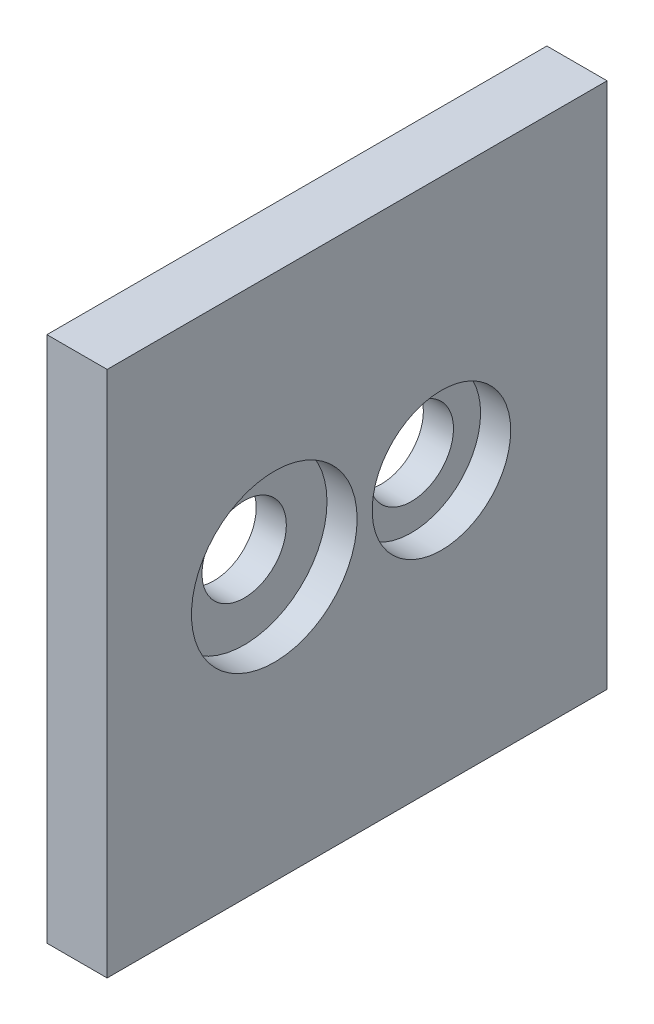
SolidWorks part; units mm, degrees
ref_plane "Front Plane" through (0, 0, 0) normal (0, 0, 1) x (1, 0, 0)
ref_plane "Top Plane" through (0, 0, 0) normal (0, 1, 0) x (1, 0, 0)
ref_plane "Right Plane" through (0, 0, 0) normal (1, 0, 0) x (0, 0, -1)
sketch "Sketch1" plane through (0, 0, 0) normal (0, 1, 0) x (1, 0, 0)
  line L0 (-55, 0) -> (55, 0) construction
  line L1 (10, 83) -> (-10, 83)
  line L2 (10, 83) -> (10, -83)
  line L3 (10, -83) -> (-10, -83)
  line L4 (-10, 83) -> (-10, -83)
  line L5 (0, -55) -> (0, 55) construction
  point P6 (-10, 0)
  point P7 (0, -83)
  dimension "D1" = 166
  dimension "D2" = 20
extrude "Boss-Extrude1" add sketch "Sketch1" along normal blind 175
sketch "Sketch2" plane through (10, 0, 0) normal (1, 0, 0) x (0, 0, -1)
  circle A0 centre (-27.5, 90.5) radius 14 construction
  circle A1 centre (28, 90.5) radius 14 construction
  circle A2 centre (-27.5, 90.5) radius 14
  circle A3 centre (28, 90.5) radius 14
extrude "Cut-Extrude1" cut sketch "Sketch2" against normal blind 175
sketch "Sketch3" plane through (10, 0, 0) normal (1, 0, 0) x (0, 0, -1)
  circle A0 centre (-27.5, 90.5) radius 27.5 construction
  circle A1 centre (28, 90.5) radius 23 construction
  circle A2 centre (-27.5, 90.5) radius 27.5
  circle A3 centre (28, 90.5) radius 23
extrude "Cut-Extrude2" cut sketch "Sketch3" against normal blind 10
